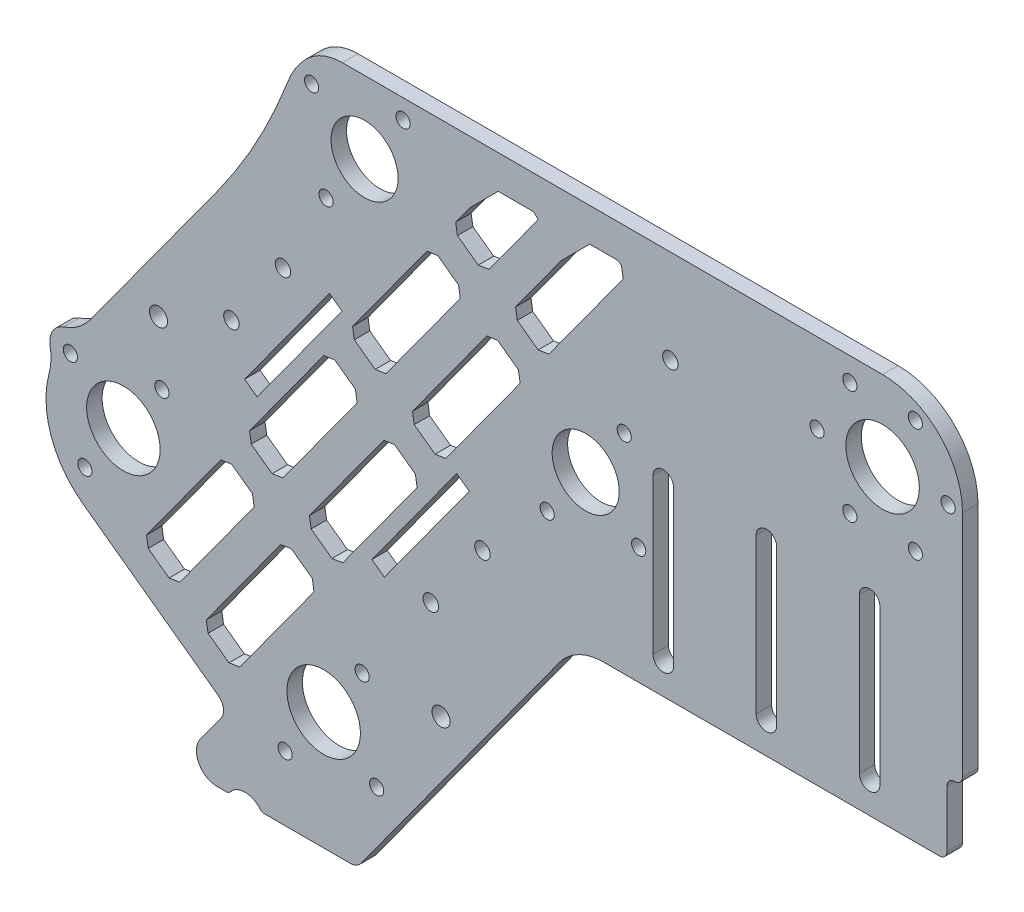
SolidWorks part; units mm, degrees
material "Liga 1060"
ref_plane "Plano frontal" through (0, 0, 0) normal (0, 0, 1) x (1, 0, 0)
ref_plane "Plano superior" through (0, 0, 0) normal (0, 1, 0) x (1, 0, 0)
ref_plane "Plano direito" through (0, 0, 0) normal (1, 0, 0) x (0, 0, -1)
sketch "Esboço1" plane through (0, 0, 0) normal (0, 0, 1) x (1, 0, 0)
  line L0 (0, 31) -> (-209, 31)
  line L1 (-209, 31) -> (-338.3128, -146.9837)
  line L2 (-232.309, -224) -> (31, -224)
  line L3 (31, -224) -> (31, 0)
  line L4 (-338.3128, -146.9837) -> (-232.309, -224)
  circle A0 centre (0, 0) radius 14.25
  circle A1 centre (0, 0) radius 25.4 construction
  arc A2 (31, 0) -> (0, 31) centre (0, 0) ccw
  circle A4 centre (25.4, 0) radius 2.75
  circle A5 centre (12.7, -21.997) radius 2.75
  circle A6 centre (-12.7, -21.997) radius 2.75
  circle A7 centre (-25.4, 0) radius 2.75
  circle A8 centre (-12.7, 21.997) radius 2.75
  circle A9 centre (12.7, 21.997) radius 2.75
  point P19 (0, 0)
  dimension "D1" = 28.5
  dimension "D2" = 50.8
  dimension "D3" = 62
  dimension "D4" = 5.5
  dimension "D6" = 54
  dimension "D7" = 240
  dimension "D8" = 255
  dimension "D9" = 220
  dimension "D5" = 6
extrude "Ressalto-extrusão1" add sketch "Esboço1" along normal blind 6
fillet "Filete1" radius 35 4 edges at (31, -224, 3) (-209, 31, 3) (-232.309, -224, 3) (-338.3128, -146.9837, 3)
sketch "Esboço2" plane through (0, 0, 6) normal (0, 0, 1) x (1, 0, 0)
  line L0 (-294.4052, -134.2968) -> (-196.8328, 0) construction
  line L1 (-196.8328, 0) -> (-119.1672, -56.4274) construction
  line L2 (-119.1672, -56.4274) -> (-216.7395, -190.7242) construction
  line L3 (-294.4052, -134.2968) -> (-255.5724, -162.5105) construction
  line L4 (-219.4822, 16.5725) -> (-317.7403, -118.6681) construction
  line L5 (-158, -28.2137) -> (-255.5724, -162.5105) construction
  line L6 (-255.5724, -162.5105) -> (-216.7395, -190.7242) construction
  line L7 (-119.1672, -56.4274) -> (-115.1221, -59.3663) construction
  line L8 (-196.8328, 0) -> (-200.8779, 2.9389) construction
  circle A0 centre (-196.8328, 0) radius 14.25 construction
  circle A1 centre (-119.1672, -56.4274) radius 14.25 construction
  circle A2 centre (-294.4052, -134.2968) radius 14.25
  circle A3 centre (-216.7395, -190.7242) radius 14.25
  circle A6 centre (-294.4052, -134.2968) radius 28 construction
  circle A7 centre (-216.7395, -190.7242) radius 28 construction
  circle A8 centre (-200.8779, 2.9389) radius 13.0072
  circle A9 centre (-115.1221, -59.3663) radius 13.0072
  dimension "D1" = 28.5
  dimension "D5" = 56
  dimension "D3" = 96
  dimension "D2" = 158
  dimension "D4" = 166
  dimension "D6" = 106
extrude "Corte-extrusão1" cut sketch "Esboço2" against normal through all
sketch "Esboço3" plane through (0, 0, 6) normal (0, 0, 1) x (1, 0, 0)
  line L0 (-191.1666, 31) -> (-215.7318, 31)
  line L1 (0, 31) -> (-191.1666, 31) construction
  line L2 (-232.3627, -1.156) -> (-219.4822, 16.5725)
  line L3 (-219.4822, 16.5725) -> (-317.7403, -118.6681) construction
  arc A0 (-215.7318, 31) -> (-232.3627, -1.156) centre (-200.8779, 2.9389) ccw
  circle A2 centre (-200.8779, 2.9389) radius 13.0072
  arc A4 (-219.4822, 16.5725) -> (-191.1666, 31) centre (-191.1666, -4) cw
  arc M21 (-191.1666, 31) -> (-219.4822, 16.5725) centre (-191.1666, -4) ccw
  line M22 (-219.4822, 16.5725) -> (-317.7403, -118.6681)
  dimension "D1" = 63.5
extrude "Ressalto-extrusão2" add sketch "Esboço3" against normal through all contours L0 A0 M22 M21 region at (-220.5245, 19.471, 6)
fillet "Filete2" radius 220 1 edges at (-232.3627, -1.156, 3)
fillet "Filete3" radius 20 1 edges at (-215.7318, 31, 3)
sketch "Esboço4" plane through (0, 0, 6) normal (0, 0, 1) x (1, 0, 0)
  line L0 (31, -189) -> (31, 0) construction
  line L1 (-220.9368, -224) -> (-4, -224) construction
  line L2 (-176.9704, -224) -> (-4, -224)
  line L3 (31, -119.6723) -> (31, -189)
  arc A0 (31, -119.6723) -> (-176.9704, -224) centre (68.0219, -452.9243) ccw
  arc A1 (-4, -224) -> (31, -189) centre (-4, -189) ccw
extrude "Corte-extrusão2" cut sketch "Esboço4" against normal through all
sketch "Esboço6" plane through (0, 0, 6) normal (0, 0, 1) x (1, 0, 0)
  line L0 (31, -119.6723) -> (-119, -119.6723)
  line L1 (31, -119.6723) -> (31, 0) construction
  line L2 (-119, -119.6723) -> (-194.7985, -224)
  line L3 (-220.9368, -224) -> (-176.9704, -224) construction
  line L4 (-258.0705, -36.5397) -> (-317.7403, -118.6681) construction
  line L5 (-194.7985, -224) -> (-176.9704, -224)
  arc A0 (31, -119.6723) -> (-176.9704, -224) centre (68.0219, -452.9243) ccw construction
  arc A1 (-176.9704, -224) -> (31, -119.6723) centre (68.0219, -452.9243) cw
  dimension "D1" = 150
extrude "Corte-extrusão3" cut sketch "Esboço6" against normal through all
fillet "Filete4" radius 21 1 edges at (-194.7985, -224, 3)
fillet "Filete5" radius 21 1 edges at (-119, -119.6723, 3)
sketch "Esboço8" plane through (0, 0, 6) normal (0, 0, 1) x (1, 0, 0)
  line L0 (-188.5092, -215.3435) -> (-203.7916, -236.3779)
  line L1 (-125.2893, -128.3288) -> (-188.5092, -215.3435) construction
  line L2 (-203.7916, -236.3779) -> (-273.7916, -236.3779)
  line L3 (-273.7916, -236.3779) -> (-253.5737, -208.5503)
  line L4 (-309.9972, -167.5562) -> (-241.5093, -217.3156) construction
  arc A0 (-205.4986, -224) -> (-188.5092, -215.3435) centre (-205.4986, -203) ccw construction
  arc A1 (-253.5737, -208.5503) -> (-188.5092, -215.3435) centre (-241.6695, -409.5207) cw
  dimension "D1" = 26
  dimension "D2" = 70
extrude "Ressalto-extrusão3" add sketch "Esboço8" against normal through all
fillet "Filete6" radius 8 1 edges at (-273.7916, -236.3779, 3)
fillet "Filete7" radius 5 3 edges at (-253.5737, -208.5503, 3) (-203.7916, -236.3779, 3) (31, -119.6723, 3)
sketch "Esboço9" plane through (0, 0, 6) normal (0, 0, 1) x (1, 0, 0)
  circle A0 centre (-247.1939, -240.4006) radius 7.5
  dimension "D1" = 15
extrude "Corte-extrusão4" cut sketch "Esboço9" against normal through all contours A0
fillet "Filete8" radius 2 2 edges at (-240.864, -236.3779, 3) (-253.5239, -236.3779, 3)
sketch "Esboço10" plane through (0, 0, 6) normal (0, 0, 1) x (1, 0, 0)
  line L0 (25, -119.6723) -> (25, -91.6723)
  line L1 (26, -119.6723) -> (-108.3, -119.6723) construction
  line L2 (25, -91.6723) -> (31, -91.6723)
  line L3 (31, -114.6723) -> (31, 0) construction
  line L4 (25, -119.6723) -> (31, -119.6723)
  line L5 (31, -119.6723) -> (31, -91.6723)
  dimension "D1" = 6
  dimension "D2" = 28
extrude "Corte-extrusão5" cut sketch "Esboço10" against normal through all
fillet "Filete9" radius 3 3 edges at (25, -119.6723, 3) (25, -91.6723, 3) (31, -91.6723, 3)
sketch "Esboço11" plane through (0, 0, 6) normal (0, 0, 1) x (1, 0, 0)
  line L0 (-294.4052, -134.2968) -> (-216.7395, -190.7242) construction
  line L1 (-294.4052, -134.2968) -> (-196.8328, 0) construction
  line L2 (-216.7395, -190.7242) -> (-119.1672, -56.4274) construction
  line L3 (-196.8328, 0) -> (-119.1672, -56.4274) construction
  line L4 (-255.5724, -162.5105) -> (-158, -28.2137) construction
  line L5 (-221.5687, -162.4943) -> (-141.6299, -52.468)
  line L6 (-266.0646, -130.1661) -> (-186.1258, -20.1398)
  line L7 (-270.9187, -126.6394) -> (-190.9799, -16.6131)
  line L8 (-216.7146, -166.021) -> (-136.7758, -55.9947)
  line L12 (-221.5687, -162.4943) -> (-216.7146, -166.021)
  line L13 (-270.9187, -126.6394) -> (-266.0646, -130.1661)
  line L14 (-190.9799, -16.6131) -> (-186.1258, -20.1398)
  line L15 (-282.6744, -142.8197) -> (-185.1021, -8.5229) construction
  line L16 (-277.8203, -146.3464) -> (-180.248, -12.0496) construction
  line L17 (-233.3244, -178.6746) -> (-135.752, -44.3778) construction
  line L18 (-228.4703, -182.2013) -> (-130.8979, -47.9045) construction
  line L19 (-141.6299, -52.468) -> (-136.7758, -55.9947)
  dimension "D1" = 166
  dimension "D6" = 20
  dimension "D7" = 20
  dimension "D2" = 27.5
  dimension "D3" = 27.5
  dimension "D4" = 6
  dimension "D5" = 6
extrude "Corte-extrusão6" cut sketch "Esboço11" against normal through all
sketch "Esboço13" plane through (0, 0, 6) normal (0, 0, 1) x (1, 0, 0)
  line L0 (-200.8779, 2.9389) -> (-221.4269, 17.8687) construction
  line L1 (-186.1258, -20.1398) -> (-190.9799, -16.6131) construction
  line L2 (-200.8779, 2.9389) -> (-185.9482, 23.488) construction
  line L3 (-200.8779, 2.9389) -> (-215.8076, -17.6101) construction
  line L4 (-200.8779, 2.9389) -> (-115.1221, -59.3663) construction
  line L5 (-294.4052, -134.2968) -> (-216.7395, -190.7242) construction
  line L6 (-158, -28.2137) -> (-255.5724, -162.5105) construction
  line L7 (-294.4052, -134.2968) -> (-314.9542, -119.3671) construction
  line L8 (-279.4754, -113.7478) -> (-294.4052, -134.2968) construction
  line L9 (-309.3349, -154.8459) -> (-294.4052, -134.2968) construction
  circle A0 centre (-200.8779, 2.9389) radius 25.4 construction
  circle A1 centre (-115.1221, -59.3663) radius 25.4 construction
  circle A2 centre (-216.7395, -190.7242) radius 25.4 construction
  circle A3 centre (-294.4052, -134.2968) radius 25.4 construction
  circle A4 centre (-221.4269, 17.8687) radius 2.75
  circle A5 centre (-215.8076, -17.6101) radius 2.75
  circle A6 centre (-185.9482, 23.488) radius 2.75
  circle A7 centre (-130.0518, -79.9153) radius 2.75
  circle A8 centre (-94.5731, -74.2961) radius 2.75
  circle A9 centre (-100.1924, -38.8173) radius 2.75
  circle A10 centre (-314.9542, -119.3671) radius 2.75
  circle A11 centre (-279.4754, -113.7478) radius 2.75
  circle A12 centre (-309.3349, -154.8459) radius 2.75
  circle A13 centre (-231.6693, -211.2732) radius 2.75
  circle A14 centre (-196.1905, -205.654) radius 2.75
  circle A15 centre (-201.8098, -170.1752) radius 2.75
  dimension "D1" = 50.8
  dimension "D2" = 5.5
  dimension "D3" = 5.5
extrude "Corte-extrusão7" cut sketch "Esboço13" against normal through all
sketch "Esboço14" plane through (0, 0, 6) normal (0, 0, 1) x (1, 0, 0)
  circle A0 centre (-314.9542, -119.3671) radius 8
  circle A1 centre (-314.9542, -119.3671) radius 2.75
  dimension "D1" = 16
extrude "Ressalto-extrusão4" add sketch "Esboço14" against normal through all
fillet "Filete10" radius 21 2 edges at (-321.1408, -124.4391, 3) (-312.6763, -111.6982, 3)
sketch "Esboço15" plane through (0, 0, 6) normal (0, 0, 1) x (1, 0, 0)
  line L0 (-214.4913, -48.9737) -> (-247.4073, -94.2787) construction
  line L1 (-214.4913, -48.9737) -> (-209.6372, -52.5004) construction
  line L2 (-247.4073, -94.2787) -> (-242.5532, -97.8054) construction
  line L3 (-209.6372, -52.5004) -> (-242.5532, -97.8054) construction
  line L4 (-190.9799, -16.6131) -> (-270.9187, -126.6394) construction
  line L5 (-214.4913, -48.9737) -> (-190.9799, -16.6131)
  line L6 (-198.0573, -130.1336) -> (-165.1413, -84.8286) construction
  line L7 (-198.0573, -130.1336) -> (-193.2032, -133.6603) construction
  line L8 (-165.1413, -84.8286) -> (-160.2872, -88.3553) construction
  line L9 (-193.2032, -133.6603) -> (-160.2872, -88.3553) construction
  line L10 (-141.6299, -52.468) -> (-221.5687, -162.4943) construction
  line L11 (-214.4913, -48.9737) -> (-209.6372, -52.5004)
  line L12 (-266.0646, -130.1661) -> (-186.1258, -20.1398) construction
  line L13 (-216.7146, -166.021) -> (-136.7758, -55.9947) construction
  line L14 (-186.1258, -20.1398) -> (-190.9799, -16.6131) construction
  line L15 (-270.9187, -126.6394) -> (-266.0646, -130.1661) construction
  line L16 (-190.9799, -16.6131) -> (-186.1258, -20.1398)
  line L17 (-209.6372, -52.5004) -> (-186.1258, -20.1398)
  line L18 (-270.9187, -126.6394) -> (-247.4073, -94.2787)
  line L19 (-270.9187, -126.6394) -> (-266.0646, -130.1661)
  line L20 (-247.4073, -94.2787) -> (-242.5532, -97.8054)
  line L21 (-266.0646, -130.1661) -> (-242.5532, -97.8054)
  line L22 (-221.5687, -162.4943) -> (-198.0573, -130.1336)
  line L23 (-221.5687, -162.4943) -> (-216.7146, -166.021)
  line L24 (-198.0573, -130.1336) -> (-193.2032, -133.6603)
  line L25 (-216.7146, -166.021) -> (-193.2032, -133.6603)
  line L26 (-165.1413, -84.8286) -> (-141.6299, -52.468)
  line L27 (-165.1413, -84.8286) -> (-160.2872, -88.3553)
  line L28 (-141.6299, -52.468) -> (-136.7758, -55.9947)
  line L29 (-160.2872, -88.3553) -> (-136.7758, -55.9947)
  point P22 (-268.4917, -128.4027)
  dimension "D1" = 40
  dimension "D2" = 40
extrude "Ressalto-extrusão5" add sketch "Esboço15" against normal through all
sketch "Esboço17" plane through (0, 0, 6) normal (0, 0, 1) x (1, 0, 0)
  line L0 (-114.9787, 31) -> (-276.7546, -191.6654) construction
  line L2 (0, 31) -> (-209.4267, 31) construction
  line L3 (-242.5532, -97.8054) -> (-209.6372, -52.5004) construction
  line L4 (-242.5532, -97.8054) -> (-220.3052, -113.9695) construction
  line L5 (-220.3052, -113.9695) -> (-198.0573, -130.1336) construction
  line L6 (-287.2154, -168.0393) -> (-274.2711, -177.4439)
  line L7 (-287.2154, -168.0393) -> (-254.8872, -123.5434)
  line L8 (-274.2711, -177.4439) -> (-241.9429, -132.9479)
  line L9 (-254.8872, -123.5434) -> (-241.9429, -132.9479)
  line L10 (-309.9972, -167.5562) -> (-257.6187, -205.6114) construction
  line L11 (-263.9966, -184.9087) -> (-231.6684, -140.4128)
  line L12 (-218.7241, -149.8174) -> (-231.6684, -140.4128)
  line L13 (-251.0523, -194.3133) -> (-218.7241, -149.8174)
  line L14 (-251.0523, -194.3133) -> (-263.9966, -184.9087)
  line L15 (-224.0272, -129.8956) -> (-191.699, -85.3996)
  line L16 (-178.7547, -94.8042) -> (-191.699, -85.3996)
  line L17 (-211.0829, -139.3001) -> (-178.7547, -94.8042)
  line L18 (-211.0829, -139.3001) -> (-224.0272, -129.8956)
  line L19 (-247.246, -113.0261) -> (-234.3017, -122.4307)
  line L20 (-247.246, -113.0261) -> (-214.9178, -68.5302)
  line L21 (-214.9178, -68.5302) -> (-201.9735, -77.9348)
  line L22 (-234.3017, -122.4307) -> (-201.9735, -77.9348)
  line L23 (-184.0578, -74.8824) -> (-151.7296, -30.3865)
  line L24 (-138.7853, -39.791) -> (-151.7296, -30.3865)
  line L25 (-171.1135, -84.287) -> (-138.7853, -39.791)
  line L26 (-171.1135, -84.287) -> (-184.0578, -74.8824)
  line L27 (-207.2766, -58.013) -> (-194.3323, -67.4175)
  line L28 (-207.2766, -58.013) -> (-174.9484, -13.517)
  line L29 (-174.9484, -13.517) -> (-162.0041, -22.9216)
  line L30 (-194.3323, -67.4175) -> (-162.0041, -22.9216)
  line L31 (-144.0884, -19.8693) -> (-111.7602, 24.6267)
  line L32 (-98.8159, 15.2221) -> (-111.7602, 24.6267)
  line L33 (-131.1441, -29.2738) -> (-98.8159, 15.2221)
  line L34 (-131.1441, -29.2738) -> (-144.0884, -19.8693)
  line L35 (-167.3072, -2.9998) -> (-154.3629, -12.4044)
  line L36 (-167.3072, -2.9998) -> (-134.979, 41.4961)
  line L37 (-134.979, 41.4961) -> (-122.0347, 32.0916)
  line L38 (-154.3629, -12.4044) -> (-122.0347, 32.0916)
  dimension "D1" = 55
  dimension "D2" = 16
  dimension "D3" = 6.35
  dimension "D4" = 13
  dimension "D5" = 4
extrude "Corte-extrusão9" cut sketch "Esboço17" against normal through all
sketch "Esboço18" plane through (0, 0, 6) normal (0, 0, 1) x (1, 0, 0)
  line L0 (-160.0048, 31) -> (-98.0795, 31)
  line L1 (-160.0048, 31) -> (-160.0048, 18)
  line L2 (-98.0795, 31) -> (-98.0795, 18)
  line L3 (-160.0048, 18) -> (-98.0795, 18)
  line L4 (-142.6049, 31) -> (-209.4267, 31) construction
  line L5 (0, 31) -> (-122.8278, 31) construction
  dimension "D1" = 13
extrude "Ressalto-extrusão6" add sketch "Esboço18" against normal through all
chamfer "Chanfro1" distance 3 angle 45 32 edges at (-131.1441, -29.2738, 3) (-144.0884, -19.8693, 3) (-98.8159, 15.2221, 3) (-116.5748, 18, 3) (-154.3629, -12.4044, 3) (-152.0499, 18, 3) (-132.2728, 18, 3) (-167.3072, -2.9998, 3) (-174.9484, -13.517, 3) (-162.0041, -22.9216, 3) (-151.7296, -30.3865, 3) (-138.7853, -39.791, 3) (-171.1135, -84.287, 3) (-184.0578, -74.8824, 3) (-207.2766, -58.013, 3) (-194.3323, -67.4175, 3) (-191.699, -85.3996, 3) (-178.7547, -94.8042, 3) (-201.9735, -77.9348, 3) (-214.9178, -68.5302, 3) (-224.0272, -129.8956, 3) (-211.0829, -139.3001, 3) (-247.246, -113.0261, 3) (-234.3017, -122.4307, 3) (-251.0523, -194.3133, 3) (-263.9966, -184.9087, 3) (-218.7241, -149.8174, 3) (-231.6684, -140.4128, 3) (-241.9429, -132.9479, 3) (-254.8872, -123.5434, 3) (-274.2711, -177.4439, 3) (-287.2154, -168.0393, 3) first distance on face at (-137.6162, -24.5715, 3) first distance on face at (-130.3316, -0.9346, 3) first distance on face at (-114.98, -7.0259, 3) first distance on face at (-109.6071, 18, 3) first distance on face at (-160.835, -7.7021, 3) first distance on face at (-142.1614, 18, 3) first distance on face at (-159.6785, 7.5001, 3) first distance on face at (-168.4762, -18.2193, 3) first distance on face at (-178.1682, -45.1696, 3) first distance on face at (-145.2575, -35.0888, 3) first distance on face at (-154.9494, -62.039, 3) first distance on face at (-177.5856, -79.5847, 3) first distance on face at (-167.8937, -52.6344, 3) first distance on face at (-191.1125, -35.765, 3) first distance on face at (-200.8044, -62.7153, 3) first distance on face at (-185.2269, -90.1019, 3) first distance on face at (-194.9188, -117.0522, 3) first distance on face at (-218.1376, -100.1827, 3) first distance on face at (-208.4456, -73.2325, 3) first distance on face at (-207.8631, -107.6476, 3) first distance on face at (-217.555, -134.5978, 3) first distance on face at (-231.0819, -90.7782, 3) first distance on face at (-240.7738, -117.7284, 3) first distance on face at (-257.5244, -189.611, 3) first distance on face at (-247.8325, -162.6608, 3) first distance on face at (-234.8882, -172.0653, 3) first distance on face at (-225.1962, -145.1151, 3) first distance on face at (-258.107, -155.1959, 3) first distance on face at (-271.0513, -145.7913, 3)
sketch "Esboço19" plane through (0, 0, 6) normal (0, 0, 1) x (1, 0, 0)
  line L0 (-247.4073, -94.2787) -> (-214.4913, -48.9737) construction
  line L1 (-247.4073, -94.2787) -> (-267.9563, -79.3489) construction
  line L2 (-214.4913, -48.9737) -> (-235.0404, -34.044) construction
  line L3 (-267.9563, -79.3489) -> (-235.0404, -34.044) construction
  line L4 (-286.6081, -97.9354) -> (-271.3257, -76.9009)
  line L5 (-271.3257, -76.9009) -> (-248.904, -93.1913)
  line L6 (-248.904, -93.1913) -> (-263.616, -113.4407)
  line L8 (-258.0705, -36.5397) -> (-307.2574, -104.2397) construction
  line L10 (-216.6811, -70.9572) -> (-245.4826, -110.5991) construction
  line L12 (-236.7287, -120.6673) -> (-221.6001, -131.6589) construction
  line L13 (-229.1644, -126.1631) -> (-196.4595, -81.1487) construction
  line L14 (-232.5383, -120.0036) -> (-203.7369, -80.3618) construction
  line L15 (-169.2847, -151.0381) -> (-191.7065, -134.7477)
  line L16 (-184.5672, -172.0725) -> (-169.2847, -151.0381)
  line L17 (-191.7065, -134.7477) -> (-206.4185, -154.9971)
  arc A0 (-286.6081, -97.9354) -> (-263.616, -113.4407) centre (-294.4052, -134.2968) cw
  circle A1 centre (-294.4052, -134.2968) radius 14.25 construction
  arc A2 (-184.5672, -172.0725) -> (-206.4185, -154.9971) centre (-216.7395, -190.7242) ccw
  dimension "D1" = 25.4
  dimension "D2" = 13
  dimension "D3" = 13
  dimension "D4" = 26
extrude "Corte-extrusão10" [suppressed] cut sketch "Esboço19" against normal through all
chamfer "Chanfro2" [suppressed] distance 5 angle 45
sketch "Esboço20" plane through (0, 0, 6) normal (0, 0, 1) x (1, 0, 0)
  line L0 (-250.9337, -226.4198) -> (-213.2201, -227.778)
  line L1 (-207.0656, -225.0727) -> (-199.6885, -216.4293)
  line L2 (-199.6885, -216.4293) -> (-251.0566, -220.3731)
  arc A0 (-213.2201, -227.778) -> (-207.0656, -225.0727) centre (-212.942, -220.0572) ccw
  arc A1 (-251.0566, -220.3731) -> (-250.9337, -226.4198) centre (-250.8247, -223.393) ccw
extrude "Corte-extrusão11" [suppressed] cut sketch "Esboço20" against normal through all
sketch "Esboço21" plane through (0, 0, 6) normal (0, 0, 1) x (1, 0, 0)
  line L0 (-5.0481, -47.4567) -> (-5.0481, -107.4567) construction
  line L1 (-1.0481, -47.4567) -> (-1.0481, -107.4567)
  line L2 (-9.0481, -47.4567) -> (-9.0481, -107.4567)
  line L3 (-45.0481, -47.4567) -> (-45.0481, -107.4567) construction
  line L4 (-41.0481, -47.4567) -> (-41.0481, -107.4567)
  line L5 (-49.0481, -47.4567) -> (-49.0481, -107.4567)
  line L6 (-85.0481, -47.4567) -> (-85.0481, -107.4567) construction
  line L7 (-81.0481, -47.4567) -> (-81.0481, -107.4567)
  line L8 (-89.0481, -47.4567) -> (-89.0481, -107.4567)
  arc A0 (-1.0481, -47.4567) -> (-9.0481, -47.4567) centre (-5.0481, -47.4567) ccw
  arc A1 (-9.0481, -107.4567) -> (-1.0481, -107.4567) centre (-5.0481, -107.4567) ccw
  arc A2 (-41.0481, -47.4567) -> (-49.0481, -47.4567) centre (-45.0481, -47.4567) ccw
  arc A3 (-49.0481, -107.4567) -> (-41.0481, -107.4567) centre (-45.0481, -107.4567) ccw
  arc A4 (-81.0481, -47.4567) -> (-89.0481, -47.4567) centre (-85.0481, -47.4567) ccw
  arc A5 (-89.0481, -107.4567) -> (-81.0481, -107.4567) centre (-85.0481, -107.4567) ccw
  point P2 (-5.0481, -77.4567)
  point P7 (-45.0481, -77.4567)
  point P16 (-85.0481, -77.4567)
  dimension "D2" = 4
  dimension "D4" = 4
  dimension "D5" = 4
  dimension "D1" = 40
  dimension "D3" = 40
  dimension "D6" = 60
  dimension "D7" = 60
  dimension "D8" = 60
extrude "Corte-extrusão12" cut sketch "Esboço21" against normal through all
sketch "Esboço22" plane through (0, 0, 6) normal (0, 0, 1) x (1, 0, 0)
  line L0 (-280.7727, -89.9036) -> (-171.2525, -169.4747) construction
  line L1 (-309.9972, -167.5562) -> (-257.6187, -205.6114) construction
  line L2 (-258.0705, -36.5397) -> (-307.2574, -104.2397) construction
  line L3 (-125.2893, -128.3288) -> (-202.2942, -234.3169) construction
  circle A0 centre (-280.7727, -89.9036) radius 3.5
  circle A1 centre (-171.2525, -169.4747) radius 3.5
  dimension "D1" = 13
  dimension "D2" = 13
  dimension "D4" = 7
  dimension "D3" = 80
extrude "Corte-extrusão13" cut sketch "Esboço22" against normal blind 10
sketch "Esboço24" plane through (0, 0, 6) normal (0, 0, 1) x (1, 0, 0)
  line L0 (-203.7369, -80.3618) -> (-193.4623, -87.8267) construction
  line L1 (-232.5383, -120.0036) -> (-203.7369, -80.3618) construction
  line L2 (-193.4623, -87.8267) -> (-189.2719, -87.163) construction
  line L3 (-193.4623, -87.8267) -> (-222.2638, -127.4685) construction
  line L4 (-232.5383, -120.0036) -> (-222.2638, -127.4685) construction
  line L5 (-232.5383, -120.0036) -> (-236.7287, -120.6673) construction
  line L6 (-227.4011, -123.7361) -> (-198.5996, -84.0942) construction
  circle A0 centre (-232.5259, -49.4676) radius 3
  circle A1 centre (-252.5106, -76.9742) radius 3
  circle A2 centre (-175.1686, -133.1664) radius 3
  circle A3 centre (-155.1839, -105.6599) radius 3
extrude "Corte-extrusão14" cut sketch "Esboço24" against normal blind 10
sketch "Esboço25" plane through (0, 0, 6) normal (0, 0, 1) x (1, 0, 0)
  circle A0 centre (-82.2985, -5.3418) radius 3
extrude "Corte-extrusão15" cut sketch "Esboço25" against normal through all
